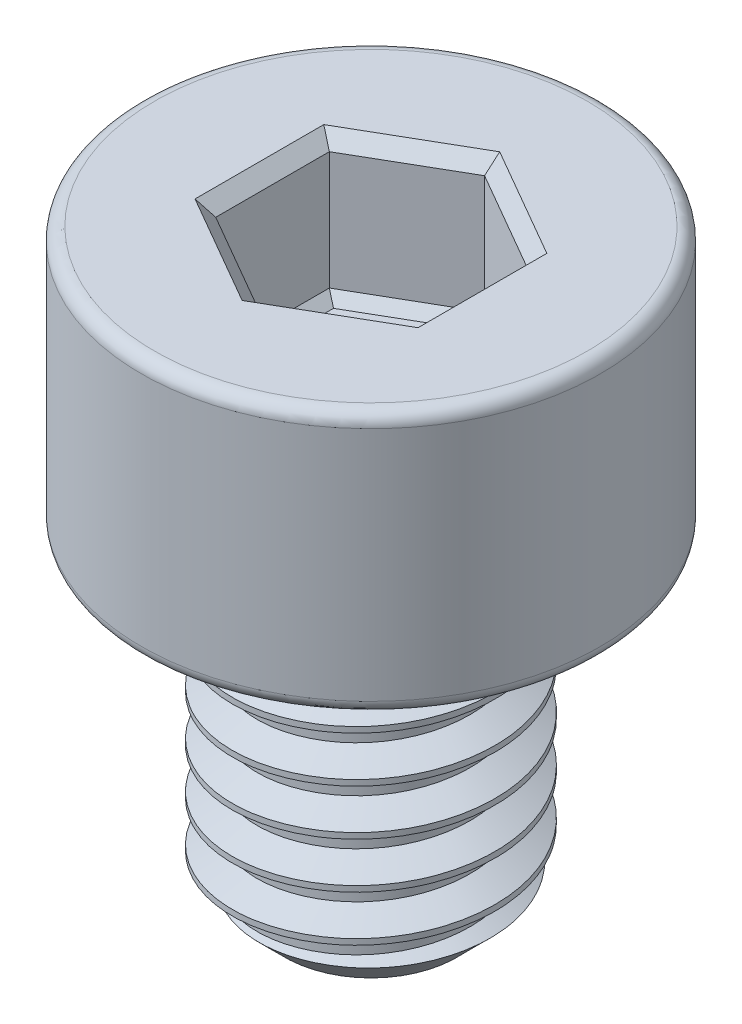
SolidWorks part; units mm, degrees
material "AISI Type A2 Tool Steel"
ref_plane "Front Plane" through (0, 0, 0) normal (0, 0, 1) x (1, 0, 0)
ref_plane "Top Plane" through (0, 0, 0) normal (0, 1, 0) x (1, 0, 0)
ref_plane "Right Plane" through (0, 0, 0) normal (1, 0, 0) x (0, 0, -1)
sketch "Sketch1" plane through (0, 0, 0) normal (0, 1, 0) x (1, 0, 0)
  circle A0 centre (0, 0) radius 2
  dimension "D1" = 4
extrude "Boss-Extrude1" add sketch "Sketch1" along normal blind 5
thread "Thread1" pitch 0.7 start angle 0, offset 1, length 0, pitch 0.7, diameter 4
ref_plane "Plane1" through (2, -1, 0) normal (0, 0, 1) x (1, 0, 0)
sketch "Thread Profile1" plane through (2, -1, 0) normal (0, 0, 1) x (1, 0, 0)
  line L0 (0, 0) -> (0, 0.7) construction
  line L11 (0, 0) -> (0, 0.6125)
  line L12 (0, 0.6125) -> (-0.3789, 0.3937)
  line L13 (-0.3789, 0.3937) -> (-0.3789, 0.2187)
  line L15 (-0.3789, 0.2187) -> (0, 0)
  line L17 (-0.3789, 0.3062) -> (0, 0.3062) construction
  point P2 (0, 0)
  dimension "Pitch" = 0.7
  dimension "Profile_Angle" = 60
  dimension "Profile_Land" = 0.175
  dimension "Profile_Height" = 0.3789
sketch "Sketch4" plane through (0, 5, 0) normal (0, -1, 0) x (-1, 0, 0)
  circle A0 centre (0, 0) radius 3.5
  dimension "D1" = 7
extrude "Boss-Extrude2" add sketch "Sketch4" against normal blind 4
fillet "Fillet1" radius 0.2 2 edges at (0, 5, -3.5) (0, 9, -3.5)
sketch "Sketch6" plane through (0, 0, 0) normal (0, 0, 1) x (1, 0, 0)
  line L0 (0, 0) -> (2.01, 0) construction
  line L1 (2.01, 0) -> (2.01, 0.7)
  line L2 (2.01, 0.7) -> (1.31, 0)
  line L3 (1.31, 0) -> (2.01, 0)
  line L4 (0, 0) -> (0, 0.3482) construction
  dimension "D1" = 0.7
  dimension "D2" = 45
  dimension "D3" = 2.01
revolve "Cut-Revolve1" cut sketch "Sketch6" angle 360 about L4
sketch "Sketch7" plane through (0, 9, 0) normal (0, 1, 0) x (1, 0, 0)
  line L1 (0, 1.7321) -> (-1.5, 0.866)
  line L2 (-1.5, 0.866) -> (-1.5, -0.866)
  line L3 (-1.5, -0.866) -> (0, -1.7321)
  line L4 (0, -1.7321) -> (1.5, -0.866)
  line L5 (1.5, -0.866) -> (1.5, 0.866)
  line L6 (1.5, 0.866) -> (0, 1.7321)
  circle A0 centre (0, 0) radius 1.5 construction
  dimension "D1" = 3
extrude "Cut-Extrude1" cut sketch "Sketch7" against normal blind 2
chamfer "Chamfer1" distance 0.2 angle 45 6 edges at (-1.5, 9, 0) (-0.75, 9, 1.299) (0.75, 9, 1.299) (1.5, 9, 0) (0.75, 9, -1.299) (-0.75, 9, -1.299)
sketch "Sketch8" plane through (0, 7, 0) normal (0, 1, 0) x (1, 0, 0)
  line L1 (0, 1.7321) -> (-1.5, 0.866)
  line L2 (-1.5, 0.866) -> (-1.5, -0.866)
  line L3 (-1.5, -0.866) -> (0, -1.7321)
  line L4 (0, -1.7321) -> (1.5, -0.866)
  line L5 (1.5, -0.866) -> (1.5, 0.866)
  line L6 (1.5, 0.866) -> (0, 1.7321)
  circle A0 centre (0, 0) radius 1.5 construction
extrude "Cut-Extrude2" cut sketch "Sketch8" against normal blind 0.15 draft 45
